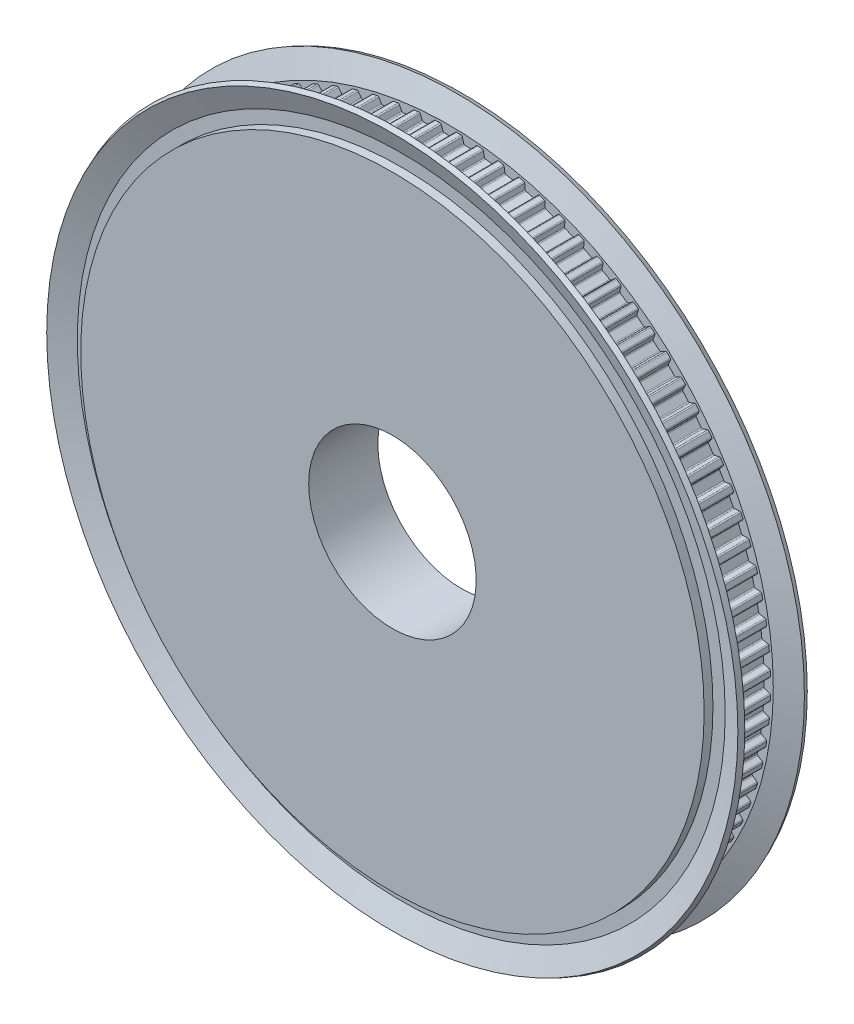
SolidWorks part; units mm, degrees
ref_plane "Front Plane" through (0, 0, 0) normal (0, 0, 1) x (1, 0, 0)
ref_plane "Top Plane" through (0, 0, 0) normal (0, 1, 0) x (1, 0, 0)
ref_plane "Right Plane" through (0, 0, 0) normal (1, 0, 0) x (0, 0, -1)
ref_axis "Axis1" through (0, 0, 55) along (0, 0, -1)
sketch "SketchRevolveGearBelt01" plane through (0, 0, 0) normal (1, 0, 0) x (0, 0, -1)
  line L0 (0, 0) -> (1, 0) construction
  line L1 (3.302, 0) -> (3.302, 29.7767)
  line L2 (3.302, 29.7767) -> (2.4606, 29.7767)
  line L3 (2.4606, 29.7767) -> (2.4606, 30.9456)
  line L4 (2.4606, 30.9456) -> (3.3162, 33.0113)
  line L5 (3.3162, 33.0113) -> (2.8469, 33.2057)
  line L6 (2.8469, 33.2057) -> (2.032, 31.0467)
  line L7 (2.032, 31.0467) -> (2.032, 30.7967)
  line L8 (2.032, 30.7967) -> (-2.032, 30.7967)
  line L9 (-2.032, 30.7967) -> (-2.032, 31.0467)
  line L10 (-2.032, 31.0467) -> (-2.8469, 33.2057)
  line L11 (-2.8469, 33.2057) -> (-3.3162, 33.0113)
  line L12 (-3.3162, 33.0113) -> (-2.4606, 30.9456)
  line L13 (-2.4606, 30.9456) -> (-2.4606, 29.7767)
  line L14 (-2.4606, 29.7767) -> (-3.302, 29.7767)
  line L15 (-3.302, 29.7767) -> (-3.302, 0)
  line L16 (-3.302, 0) -> (3.302, 0)
  dimension "GearBeltSide1" = 3.302
  dimension "GearBeltFlange1OutsideWidth" = 2.4606
  dimension "GearBeltFlange1OutsideLength" = 1.169
  dimension "GearBeltFlange1X" = 0.8556
  dimension "GearBeltFlange1Y" = 2.0656
  dimension "GearBeltFlangeThickness" = 1.821
  dimension "GearBeltToothWidth1" = 2.032
  dimension "GearBeltFlangeInside" = 0.25
  dimension "GearBeltOutsideDiameter" = 30.7967
  dimension "GearBeltToothWidth2" = 2.032
  dimension "GearBeltFlange2X" = 0.8556
  dimension "GearBeltFlange2OutsideWidth" = 2.4606
revolve "GearBelt01" add sketch "SketchRevolveGearBelt01" angle 360 about L0
sketch "SketchToothGearBelt01" plane through (0, 0, 0) normal (0, 0, 1) x (1, 0, 0)
  line L0 (-0.6657, 30.7031) -> (-0.499, 30.2452)
  line L1 (-0.3797, 30.1617) -> (0.3797, 30.1617)
  line L2 (0.499, 30.2452) -> (0.6657, 30.7031)
  line L3 (0.7883, 30.7866) -> (0, 33.3266)
  line L4 (0, 33.3266) -> (-0.7883, 30.7866)
  arc A0 (-0.7883, 30.7866) -> (-0.6657, 30.7031) centre (-0.785, 30.6596) cw
  arc A1 (-0.499, 30.2452) -> (-0.3797, 30.1617) centre (-0.3797, 30.2887) ccw
  arc A2 (0.3797, 30.1617) -> (0.499, 30.2452) centre (0.3797, 30.2887) ccw
  arc A3 (0.6657, 30.7031) -> (0.7883, 30.7866) centre (0.785, 30.6596) cw
  dimension "GearBeltToothR1" = 0.254
  dimension "GearBeltToothR2" = 0.254
  dimension "GearBeltToothX1" = 0.1666
  dimension "GearBeltToothY1" = 0.4578
  dimension "GearBeltToothRootX" = 30.1617
  dimension "GearBeltToothRootY" = 30.1617
  dimension "GearBeltToothX2" = 0.1666
  dimension "GearBeltToothY2" = 0.4578
  dimension "GearBeltToothCapX1" = 0.7883
  dimension "GearBeltToothCapY1" = 2.54
  dimension "GearBeltToothCapX2" = 0.7883
  dimension "GearBeltToothCapY2" = 2.54
extrude "ToothExtrudeCutGearBelt01" cut sketch "SketchToothGearBelt01" against normal blind 2.032 and the other way blind 2.032
pattern_circular "PatternGearBelt01" count 96 every 3.75 about axis through (0, 0, 55) along (0, 0, -1) of "ToothExtrudeCutGearBelt01"
sketch "BoreRevolveSketch" plane through (0, 0, 0) normal (1, 0, 0) x (0, 0, -1)
  line L0 (0, 0) -> (1, 0) construction
  line L1 (-3.302, 0) -> (3.302, 0)
  line L2 (3.302, 0) -> (3.302, 7.75)
  line L3 (3.302, 7.75) -> (-3.302, 7.75)
  line L4 (-3.302, 7.75) -> (-3.302, 0)
  dimension "BoreSide1" = 3.302
  dimension "TaperSide1" = 7.75
  dimension "BoreSide2" = 3.302
  dimension "TaperSide2" = 7.75
revolve "BoreRevolveCut" cut sketch "BoreRevolveSketch" angle 360 about L0
sketch "AuxiliarySketchGearBelt01" plane through (0, 0, 0) normal (0, 0, 1) x (1, 0, 0)
  circle A0 centre (0, 0) radius 31.0467 construction
  dimension "PitchDiameter" = 62.0933
sketch "Sketch1" plane through (0, 0, -3.302) normal (0, 0, -1) x (-1, 0, 0)
  circle A0 centre (0, 0) radius 8
  dimension "D1" = 16
extrude "Cut-Extrude1" cut sketch "Sketch1" against normal blind 10
